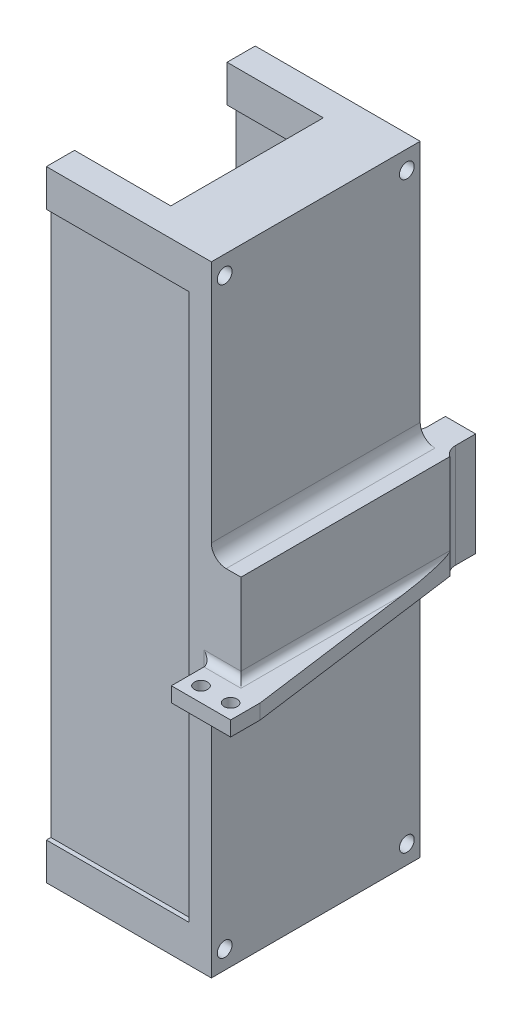
SolidWorks part; units mm, degrees
ref_plane "Front Plane" through (0, 0, 0) normal (0, 0, 1) x (1, 0, 0)
ref_plane "Top Plane" through (0, 0, 0) normal (0, 1, 0) x (1, 0, 0)
ref_plane "Right Plane" through (0, 0, 0) normal (1, 0, 0) x (0, 0, -1)
sketch "Sketch1" plane through (0, 0, 0) normal (0, 1, 0) x (1, 0, 0)
  line L0 (-2.54, 2.54) -> (-2.54, 40.132)
  line L1 (-2.54, -2.54) -> (7.62, -2.54)
  line L2 (-2.54, -2.54) -> (-2.54, 2.54)
  line L3 (-2.54, 2.54) -> (7.62, 2.54) construction
  line L4 (7.62, -2.54) -> (7.62, 2.54)
  line L5 (-2.54, 40.132) -> (2.54, 40.132)
  line L6 (2.54, 40.132) -> (7.62, 2.54)
  circle A0 centre (0, 0) radius 1.1303
  circle A1 centre (5.08, 0) radius 1.1303
  dimension "D1" = 2.2606
  dimension "D3" = 2.54
  dimension "D2" = 5.08
  dimension "D4" = 2.54
  dimension "D5" = 2.54
  dimension "D6" = 2.54
  dimension "D7" = 42.672
  dimension "D8" = 5.08
extrude "Boss-Extrude1" add sketch "Sketch1" along normal blind 2.54
sketch "Sketch2" plane through (0, 2.54, 0) normal (0, 1, 0) x (1, 0, 0)
  line L0 (-2.54, -2.54) -> (7.62, -2.54) construction
  line L1 (-2.54, 40.132) -> (2.54, 40.132)
  line L2 (-2.54, 40.132) -> (-2.54, 4.318)
  line L3 (-2.54, 4.318) -> (2.54, 4.318)
  line L4 (2.54, 40.132) -> (2.54, 4.318)
  dimension "D1" = 6.858
extrude "Boss-Extrude2" add sketch "Sketch2" along normal blind 15.24
ref_plane "Plane1" through (0, 8.89, 0) normal (0, 1, 0) x (1, 0, 0)
sketch "Sketch3" plane through (-2.54, 0, 0) normal (-1, 0, 0) x (0, 0, 1)
  line L0 (-40.132, 17.78) -> (-40.132, 0) construction
  line L1 (-40.132, 62.0753) -> (-4.318, 62.0753)
  line L2 (-40.132, 62.0753) -> (-40.132, -44.2953)
  line L3 (-40.132, -44.2953) -> (-4.318, -44.2953)
  line L4 (-4.318, 62.0753) -> (-4.318, -44.2953)
  line L5 (-4.318, 17.78) -> (-4.318, 2.54) construction
  line L6 (6.2865, 8.89) -> (-6.2865, 8.89) construction
  dimension "D1" = 53.1853
  dimension "D2" = 53.1853
extrude "Boss-Extrude3" add sketch "Sketch3" along normal blind 3.81
fillet "Fillet1" radius 1.27 3 edges at (0, 2.54, -4.318) (2.54, 2.54, -22.225) (-2.54, 1.27, -4.318)
sketch "Sketch4" plane through (0, 0, -40.132) normal (0, 0, -1) x (-1, 0, 0)
  line L0 (-2.54, 17.78) -> (2.54, 17.78) construction
  line L1 (-1.381, 17.78) -> (3.81, 17.78)
  line L2 (-1.381, 17.78) -> (-1.381, 0)
  line L3 (-1.381, 0) -> (3.81, 0)
  line L4 (3.81, 17.78) -> (3.81, 0)
  line L5 (6.35, 62.0753) -> (6.35, -44.2953) construction
  line L6 (-2.54, 17.78) -> (-2.54, 3.81) construction
  line L7 (-2.54, 0) -> (2.54, 0) construction
  dimension "D1" = 2.54
  dimension "D2" = 1.159
extrude "Boss-Extrude4" add sketch "Sketch4" along normal blind 5.588
sketch "Sketch5" plane through (-6.35, 0, 0) normal (-1, 0, 0) x (0, 0, 1)
  line L0 (-4.318, -44.2953) -> (-4.318, 62.0753) construction
  line L1 (-40.132, -44.2953) -> (-4.318, -44.2953)
  line L2 (-40.132, -44.2953) -> (-40.132, -37.9453)
  line L3 (-40.132, -37.9453) -> (-4.318, -37.9453)
  line L4 (-4.318, -44.2953) -> (-4.318, -37.9453)
  line L5 (-40.132, 62.0753) -> (-40.132, -44.2953) construction
  line L6 (-4.318, 62.0753) -> (-40.132, 62.0753)
  line L7 (-4.318, 62.0753) -> (-4.318, 55.7253)
  line L8 (-4.318, 55.7253) -> (-40.132, 55.7253)
  line L9 (-40.132, 62.0753) -> (-40.132, 55.7253)
  dimension "D1" = 6.35
extrude "Boss-Extrude5" add sketch "Sketch5" along normal blind 7.9756
sketch "Sketch6" plane through (-14.3256, 0, 0) normal (-1, 0, 0) x (0, 0, 1)
  line L0 (-40.132, 55.7253) -> (-4.318, 55.7253) construction
  line L1 (-40.132, 62.0753) -> (-35.306, 62.0753)
  line L2 (-40.132, 62.0753) -> (-40.132, 55.7253)
  line L3 (-40.132, 55.7253) -> (-35.306, 55.7253)
  line L4 (-35.306, 62.0753) -> (-35.306, 55.7253)
  line L5 (-40.132, 55.7253) -> (-4.318, 55.7253) construction
  line L6 (-4.318, 62.0753) -> (-9.144, 62.0753)
  line L7 (-4.318, 62.0753) -> (-4.318, 55.7253)
  line L8 (-4.318, 55.7253) -> (-9.144, 55.7253)
  line L9 (-9.144, 62.0753) -> (-9.144, 55.7253)
  line L10 (-40.132, -44.2953) -> (-4.318, -44.2953) construction
  line L11 (-40.132, -37.9453) -> (-35.306, -37.9453)
  line L12 (-40.132, -37.9453) -> (-40.132, -44.2953)
  line L13 (-40.132, -44.2953) -> (-35.306, -44.2953)
  line L14 (-35.306, -37.9453) -> (-35.306, -44.2953)
  line L15 (-4.318, -37.9453) -> (-40.132, -37.9453) construction
  line L16 (-4.318, -44.2953) -> (-9.144, -44.2953)
  line L17 (-4.318, -44.2953) -> (-4.318, -37.9453)
  line L18 (-4.318, -37.9453) -> (-9.144, -37.9453)
  line L19 (-9.144, -44.2953) -> (-9.144, -37.9453)
  dimension "D1" = 4.826
extrude "Boss-Extrude6" add sketch "Sketch6" along normal blind 16.51
ref_plane "Plane2" through (0, 0, -22.225) normal (0, 0, 1) x (1, 0, 0)
sketch "Sketch7" plane through (0, 0, -4.318) normal (0, 0, 1) x (1, 0, 0)
  line L1 (-6.35, -37.9453) -> (-30.8356, -37.9453)
  line L2 (-6.35, -37.9453) -> (-6.35, 55.7253)
  line L3 (-6.35, 55.7253) -> (-30.8356, 55.7253)
  line L4 (-30.8356, -37.9453) -> (-30.8356, 55.7253)
extrude "Boss-Extrude8" add sketch "Sketch7" against normal blind 2.54 from offset 0.762 offset against normal yes
mirror "Mirror2" about plane through (0, 0, -22.225) normal (0, 0, 1) of "Boss-Extrude8"
fillet "Fillet2" radius 2.54 6 edges at (-6.35, -37.9453, -22.225) (-6.35, 55.7253, -22.225) (-2.54, 17.78, -22.225) (-2.54, 0, -22.225) (1.381, 8.89, -40.132) (-3.81, 8.89, -40.132)
sketch "Sketch8" plane through (-30.8356, 0, 0) normal (-1, 0, 0) x (0, 0, 1)
  line L0 (-4.318, -44.2953) -> (-4.318, -37.9453) construction
  line L1 (-40.132, -37.9453) -> (-40.132, -44.2953) construction
  line L2 (-40.132, -44.2953) -> (-35.306, -44.2953) construction
  line L3 (-35.306, 62.0753) -> (-40.132, 62.0753) construction
  circle A0 centre (-37.846, 58.9003) radius 1.27
  circle A1 centre (-6.604, 58.9003) radius 1.27
  circle A2 centre (-37.846, -41.1203) radius 1.27
  circle A3 centre (-6.604, -41.1203) radius 1.27
  dimension "D1" = 2.54
  dimension "D2" = 2.286
  dimension "D3" = 2.286
  dimension "D4" = 3.175
  dimension "D5" = 3.175
extrude "Cut-Extrude1" cut sketch "Sketch8" against normal through all
